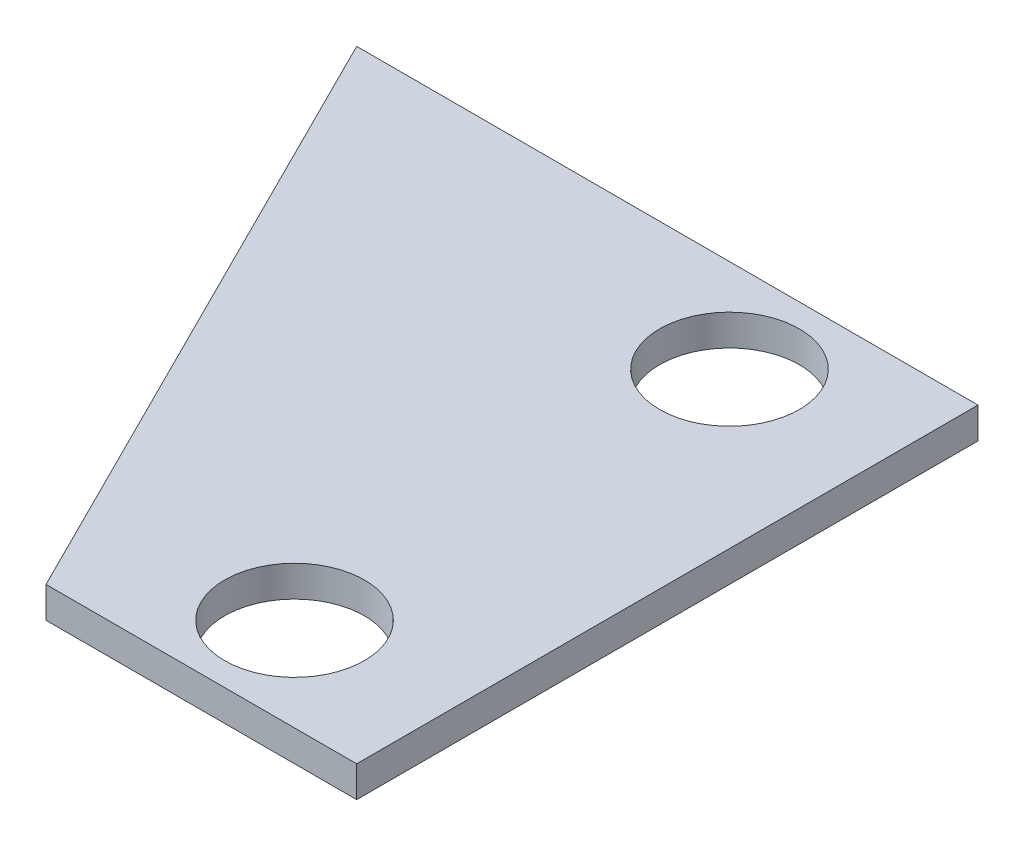
SolidWorks part; units mm, degrees
ref_plane "Ebene vorne" through (0, 0, 0) normal (0, 0, 1) x (1, 0, 0)
ref_plane "Ebene oben" through (0, 0, 0) normal (0, 1, 0) x (1, 0, 0)
ref_plane "Ebene rechts" through (0, 0, 0) normal (1, 0, 0) x (0, 0, -1)
sketch "Sketch1" plane through (0, 0, 0) normal (0, 1, 0) x (1, 0, 0)
  line L0 (0, 12.139) -> (0, -13.3155) construction
  line L1 (13.1551, 0) -> (-11.6578, 0) construction
  line L2 (-5, -10) -> (-15, 10)
  line L3 (-5, 10) -> (5, 10)
  line L4 (-5, 10) -> (-5, -10) construction
  line L5 (-5, -10) -> (5, -10)
  line L6 (5, 10) -> (5, -10)
  line L7 (-15, 10) -> (-5, 10)
  circle A0 centre (0, 7) radius 2.25
  circle A1 centre (0, -7) radius 2.25
  dimension "D4" = 4.5
  dimension "D1" = 20
  dimension "D2" = 10
  dimension "D3" = 10
  dimension "D5" = 14
extrude "Boss-Extrude1" add sketch "Sketch1" along normal blind 1
